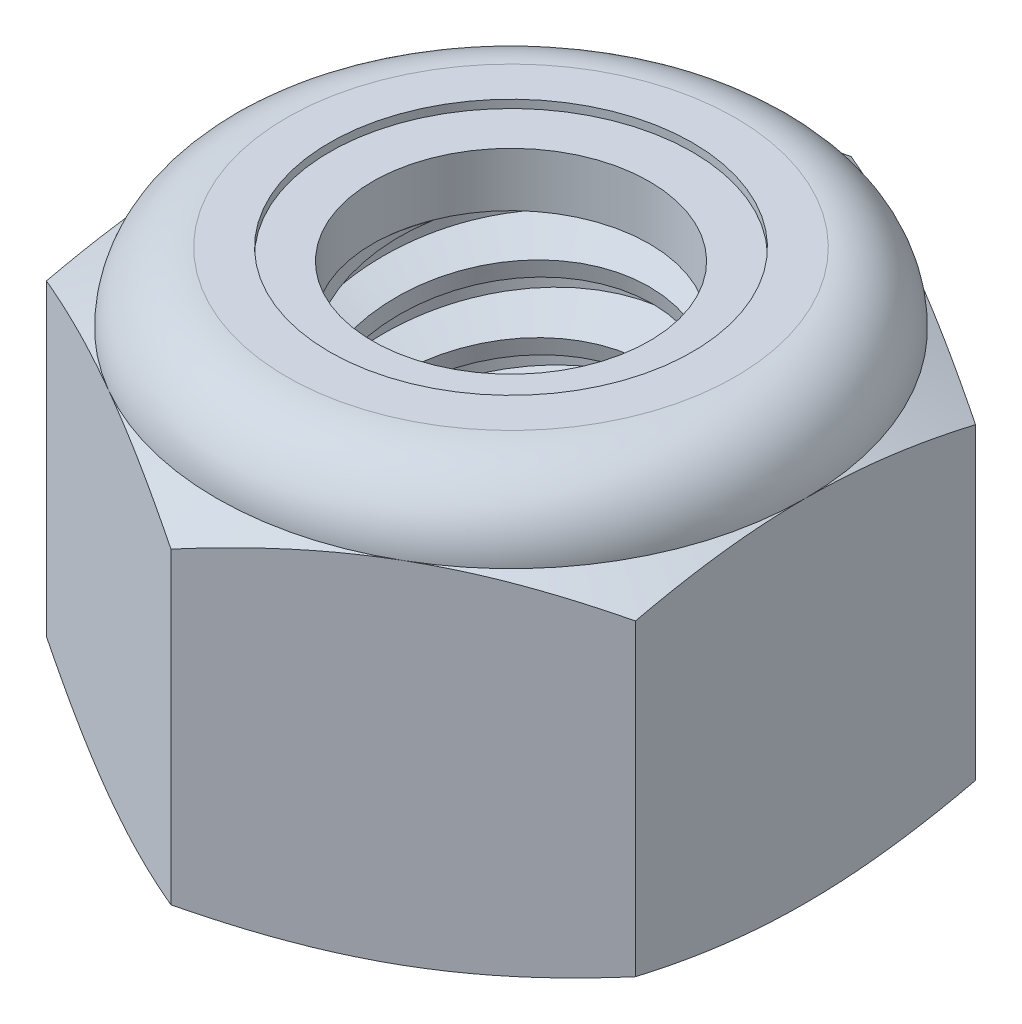
SolidWorks part; units mm, degrees
material "Plain Carbon Steel"
ref_plane "Front" through (0, 0, 0) normal (0, 0, 1) x (1, 0, 0)
ref_plane "Top" through (0, 0, 0) normal (0, 1, 0) x (1, 0, 0)
ref_plane "Right" through (0, 0, 0) normal (1, 0, 0) x (0, 0, -1)
sketch "Sketch1" plane through (0, 0, 0) normal (0, 1, 0) x (1, 0, 0)
  line L1 (0, 6.4158) -> (-5.5563, 3.2079)
  line L2 (-5.5563, 3.2079) -> (-5.5563, -3.2079)
  line L3 (-5.5563, -3.2079) -> (0, -6.4158)
  line L4 (0, -6.4158) -> (5.5562, -3.2079)
  line L5 (5.5562, -3.2079) -> (5.5562, 3.2079)
  line L6 (5.5562, 3.2079) -> (0, 6.4158)
  circle A0 centre (0, 0) radius 5.5563 construction
  dimension "Hex Flats" = 11.1125
extrude "Extrude1" add sketch "Sketch1" along normal blind 7.9375
sketch "Sketch2" plane through (0, 0, 0) normal (1, 0, 0) x (0, 0, -1)
  line L0 (-3.175, 0) -> (-3.175, 7.9375) construction
  line L1 (0, 0) -> (3.175, 0)
  line L2 (0, 0) -> (0, 7.9375)
  line L3 (0, 7.9375) -> (3.175, 7.9375)
  line L4 (3.175, 0) -> (3.175, 7.9375)
  line L5 (-3.2079, 7.9375) -> (3.2079, 7.9375) construction
  line L7 (0, -3.175) -> (0, 0) construction
  dimension "Thread Dia" = 6.35
revolve "Revolve1" add sketch "Sketch2" angle 360 about L7
sketch "Sketch3" plane through (0, 0, 0) normal (1, 0, 0) x (0, 0, -1)
  line L0 (3.175, 7.9375) -> (-3.175, 7.9375) construction
  line L1 (-3.175, 7.9375) -> (-3.175, 6.6675) construction
  line L2 (-3.175, 6.6675) -> (3.175, 7.9375) construction
  line L3 (3.175, 7.9375) -> (3.2061, 7.7818) construction
  line L4 (3.2061, 7.7818) -> (3.4241, 6.6922)
  line L5 (3.4241, 6.6922) -> (2.6722, 6.9465)
  line L6 (2.6722, 6.9465) -> (2.6099, 7.2579)
  line L7 (2.6099, 7.2579) -> (3.2061, 7.7818)
  line L8 (2.641, 7.1022) -> (3.3151, 7.237) construction
  line L9 (3.175, 7.9375) -> (3.175, 7.209) construction
  line L10 (3.175, 7.209) -> (-3.175, 5.939) construction
  line L11 (-3.175, 5.939) -> (-3.175, 6.6675) construction
  line L12 (-0.2727, 7.9375) -> (0.2727, 5.2105) construction
  line L13 (-3.175, 0) -> (-3.175, 7.9375) construction
  line L14 (0, 7.9375) -> (3.175, 7.9375) construction
  line L15 (3.175, 0) -> (3.175, 7.9375) construction
  point P13 (0, 6.574)
  dimension "D1" = 0.1588
  dimension "D2" = 0.3175
  dimension "Thread Pitch" = 1.27
  dimension "D4" = 60
  dimension "D5" = 1.27
revolve "Cut-Revolve1" cut sketch "Sketch3" angle 360 about L12
pattern_linear "LPattern1" count 6 spacing 1.27 along (0, -1, 0) count 2 spacing 1.27 along (0, 1, 0) of "Cut-Revolve1"
sketch "Sketch4" plane through (0, 0, 0) normal (1, 0, 0) x (0, 0, -1)
  line L0 (0, 7.9375) -> (3.175, 7.9375)
  line L1 (3.175, 7.9375) -> (2.6099, 7.674)
  line L2 (2.6099, 7.674) -> (2.6099, 0.2635)
  line L3 (2.6099, 0.2635) -> (3.175, 0)
  line L4 (3.175, 0) -> (0, 0)
  line L5 (0, 0) -> (0, 7.9375)
  line L6 (3.175, 0) -> (3.175, 7.9375) construction
  line L7 (0, 7.9375) -> (3.175, 7.9375) construction
  line L8 (0, 0) -> (3.175, 0) construction
  line L9 (0, 0) -> (0, 7.9375) construction
  line L10 (0, 7.9375) -> (0, 8.561) construction
  dimension "D1" = 25
revolve "Cut-Revolve2" cut sketch "Sketch4" angle 360 about L10
combine bodies "Combine1" operation type subtract main body 112 bodies to subtract 111
sketch "Sketch5" plane through (0, 0, 0) normal (1, 0, 0) x (0, 0, -1)
  line L0 (0, 0) -> (5.5563, 0)
  line L1 (5.5563, 0) -> (6.4158, 0.4008)
  line L2 (6.4158, 0.4008) -> (6.4158, 6.2138)
  line L3 (6.4158, 6.2138) -> (5.5563, 6.6146)
  line L4 (4.2333, 7.9375) -> (4.2333, 9.2075)
  line L5 (4.2333, 9.2075) -> (7.6858, 9.2075)
  line L6 (7.6858, 9.2075) -> (7.6858, -1.27)
  line L7 (7.6858, -1.27) -> (0, -1.27)
  line L8 (0, -1.27) -> (0, 0)
  line L9 (5.5563, 6.6146) -> (5.5563, 0) construction
  line L10 (0, 0) -> (3.175, 0) construction
  line L13 (6.4158, 3.3073) -> (7.6858, 3.3073) construction
  line L14 (6.4158, 7.9375) -> (6.4158, 0) construction
  line L15 (0, 0) -> (0, 9.2075) construction
  line L20 (0, 9.2075) -> (4.2333, 9.2075) construction
  line L22 (0, 7.9375) -> (3.175, 7.9375) construction
  arc A0 (5.5563, 6.6146) -> (4.2333, 7.9375) centre (4.2333, 6.6146) ccw
  dimension "D1" = 25
  dimension "D2" = 1.27
  dimension "D3" = 7.9375
  dimension "D4" = 1.3229
revolve "Cut-Revolve3" cut sketch "Sketch5" angle 360 about L15
sketch "Sketch6" plane through (0, 0, 0) normal (1, 0, 0) x (0, 0, -1)
  line L0 (0, 6.6146) -> (5.4039, 6.6146)
  line L1 (4.2333, 7.7851) -> (3.4216, 7.7851)
  line L2 (0, 9.2075) -> (0, 6.6146)
  line L3 (3.4216, 9.2075) -> (0, 9.2075)
  line L4 (0, 9.2075) -> (4.2333, 9.2075) construction
  line L5 (0, 0) -> (0, 9.2075) construction
  line L6 (0, 9.2075) -> (0, 44.323) construction
  line L7 (3.4216, 7.7851) -> (3.4216, 9.2075)
  line L8 (4.2333, 7.9375) -> (4.2333, 7.7851) construction
  line L9 (3.4216, 7.7851) -> (2.6099, 7.7851) construction
  line L10 (2.6099, 7.7851) -> (2.6099, 7.674) construction
  arc A0 (5.4039, 6.6146) -> (4.2333, 7.7851) centre (4.2333, 6.6146) ccw
  arc A1 (5.5563, 6.6146) -> (4.2333, 7.9375) centre (4.2333, 6.6146) ccw construction
  dimension "D1" = 0.1524
revolve "Cut-Revolve4" cut sketch "Sketch6" angle 360 about L6
sketch "Sketch7" plane through (0, 0, 0) normal (1, 0, 0) x (0, 0, -1)
  line L0 (2.6099, 6.6908) -> (5.325, 6.6908)
  line L1 (4.2333, 7.7089) -> (2.6099, 7.7089)
  line L2 (2.6099, 7.7089) -> (2.6099, 6.6908)
  line L3 (2.6099, 6.6908) -> (0, 6.6908) construction
  line L4 (0, 6.6908) -> (0, 7.7089) construction
  line L5 (0, 7.7089) -> (2.6099, 7.7089) construction
  line L6 (2.6099, 6.6908) -> (2.6099, 6.6146) construction
  line L7 (0, 6.6146) -> (5.4039, 6.6146) construction
  line L8 (4.2333, 7.7089) -> (4.2333, 7.7851) construction
  arc A0 (5.325, 6.6908) -> (4.2333, 7.7089) centre (4.2333, 6.6146) ccw
  arc A2 (5.4039, 6.6146) -> (4.2333, 7.7851) centre (4.2333, 6.6146) ccw construction
  dimension "D1" = 0.0762
revolve "Revolve2" add sketch "Sketch7" angle 360 about L4
equation "\"D1@Sketch3\"=\"Thread Pitch@Sketch3\"/8"
equation "\"D2@Sketch3\"=\"Thread Pitch@Sketch3\"/4"
equation "\"D5@Sketch3\"=\"Thread Pitch@Sketch3\""
equation "\"D4@LPattern1\"=\"Thread Pitch@Sketch3\""
equation "\"D3@LPattern1\"=\"Thread Pitch@Sketch3\""
equation "\"D1@LPattern1\"=\"Height@Extrude1\"/\"Thread Pitch@Sketch3\""
equation "\"D4@Sketch5\"=\"Height@Extrude1\"/6"
